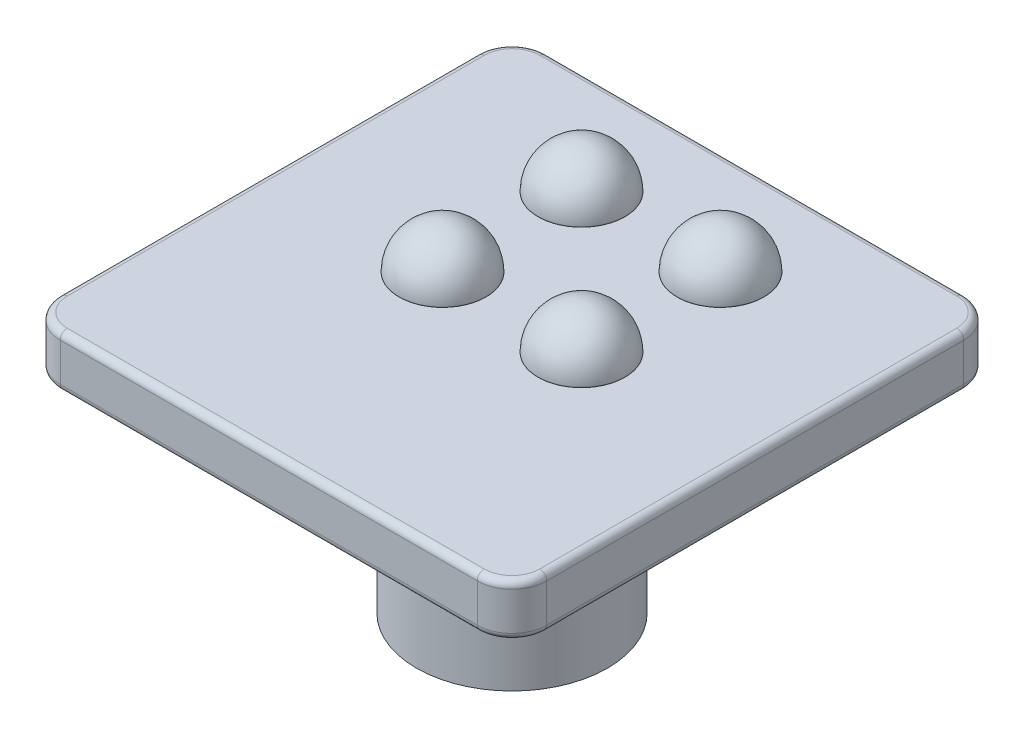
SolidWorks part; units mm, degrees
ref_plane "Front Plane" through (0, 0, 0) normal (0, 0, 1) x (1, 0, 0)
ref_plane "Top Plane" through (0, 0, 0) normal (0, 1, 0) x (1, 0, 0)
ref_plane "Right Plane" through (0, 0, 0) normal (1, 0, 0) x (0, 0, -1)
sketch "Sketch1" plane through (0, 0, 0) normal (0, 1, 0) x (1, 0, 0)
  line L1 (-7.3247, 4.3967) -> (4.6753, 4.3967)
  line L2 (-8.3247, 3.3967) -> (-8.3247, -8.6033)
  line L3 (-7.3247, -9.6033) -> (4.6753, -9.6033)
  line L4 (5.6753, 3.3967) -> (5.6753, -8.6033)
  arc A0 (-8.3247, -8.6033) -> (-7.3247, -9.6033) centre (-7.3247, -8.6033) ccw
  arc A1 (4.6753, -9.6033) -> (5.6753, -8.6033) centre (4.6753, -8.6033) ccw
  arc A2 (4.6753, 4.3967) -> (5.6753, 3.3967) centre (4.6753, 3.3967) cw
  arc A3 (-7.3247, 4.3967) -> (-8.3247, 3.3967) centre (-7.3247, 3.3967) ccw
  point P8 (5.6753, -9.6033)
  point P11 (5.6753, 4.3967)
  point P14 (-8.3247, 4.3967)
  dimension "D3" = 1
  dimension "D1" = 14
  dimension "D2" = 14
extrude "Boss-Extrude1" add sketch "Sketch1" along normal blind 1.5
sketch "Sketch2" plane through (0, 0, 0) normal (0, -1, 0) x (1, 0, 0)
  line L0 (-7.3247, 9.6033) -> (4.6753, 9.6033) construction
  line L1 (5.6753, 8.6033) -> (5.6753, -3.3967) construction
  line L2 (-1.3247, -4.3967) -> (-1.3247, 9.6033) construction
  line L3 (-8.3247, 2.6033) -> (5.6753, 2.6033) construction
  line L4 (-8.3247, -3.3967) -> (-8.3247, 8.6033) construction
  circle A0 centre (-1.3247, 2.6033) radius 2.75
  dimension "D1" = 7
  dimension "D2" = 7
extrude "Boss-Extrude2" add sketch "Sketch2" along normal blind 6
sketch "Sketch3" plane through (0, -6, 0) normal (0, -1, 0) x (1, 0, 0)
  line L0 (-1.3247, 5.3533) -> (-1.3247, -0.1467) construction
  line L1 (-3.3247, 3.1533) -> (0.6753, 3.1533)
  line L2 (-3.3247, 3.1533) -> (-3.3247, 2.0533)
  line L3 (-3.3247, 2.0533) -> (0.6753, 2.0533)
  line L4 (0.6753, 3.1533) -> (0.6753, 2.0533)
  line L5 (-1.8747, 4.6033) -> (-0.7747, 4.6033)
  line L6 (-1.8747, 4.6033) -> (-1.8747, 0.6033)
  line L7 (-1.8747, 0.6033) -> (-0.7747, 0.6033)
  line L8 (-0.7747, 4.6033) -> (-0.7747, 0.6033)
  line L9 (-4.0747, 2.6033) -> (1.4253, 2.6033) construction
  circle A3 centre (-1.3247, 2.6033) radius 2.75 construction
  circle A4 centre (-1.3247, 2.6033) radius 2.75 construction
  dimension "D7" = 0.55
  dimension "D1" = 4
  dimension "D2" = 1.1
  dimension "D3" = 1.1
  dimension "D4" = 4
  dimension "D5" = 2
  dimension "D6" = 2
  dimension "D8" = 0.55
extrude "Cut-Extrude1" cut sketch "Sketch3" against normal blind 6 contours L8 L5 L6 L1 | L1 L8 L3 L4 | L8 L1 L6 L3 | L6 L1 L2 L3 | L8 L3 L6 L7 region at (-2.5997, -6, 2.6033) region at (-1.3247, -6, 3.8783) region at (-1.3247, -6, 2.6033) region at (-0.0497, -6, 2.6033) region at (-1.3247, -6, 1.3283)
chamfer "Chamfer1" distance 0.3 angle 45 12 edges at (-1.3247, -6, 0.6033) (-1.8747, -6, 1.3283) (-2.5997, -6, 2.0533) (-3.3247, -6, 2.6033) (-2.5997, -6, 3.1533) (-0.7747, -6, 1.3283) (-0.0497, -6, 2.0533) (0.6753, -6, 2.6033) (-0.0497, -6, 3.1533) (-0.7747, -6, 3.8783) (-1.3247, -6, 4.6033) (-1.8747, -6, 3.8783)
fillet "Fillet1" radius 1 1 edges at (-1.3247, 0, -0.1467)
sketch "Sketch4" plane through (0, 1.5, 0) normal (0, 1, 0) x (1, 0, 0)
  line L0 (-1.3247, 4.3967) -> (-1.3247, -9.6033) construction
  line L1 (4.6753, 4.3967) -> (-7.3247, 4.3967) construction
  line L2 (-7.3247, -9.6033) -> (4.6753, -9.6033) construction
  line L3 (5.6753, -2.6033) -> (-8.3247, -2.6033) construction
  line L4 (-8.3247, 3.3967) -> (-8.3247, -8.6033) construction
  line L5 (5.6753, -8.6033) -> (5.6753, 3.3967) construction
  line L6 (-3.3247, 4.3967) -> (-3.3247, -9.6033) construction
  line L7 (0.6753, 4.3967) -> (0.6753, -9.6033) construction
  line L8 (-8.3247, 1.3967) -> (5.6753, 1.3967) construction
  line L9 (5.6753, -6.6033) -> (-8.3247, -6.6033) construction
  circle A0 centre (-3.3247, 1.3967) radius 1.25
  circle A1 centre (0.6753, -2.6033) radius 1.25
  circle A2 centre (-3.3247, -2.6033) radius 1.25
  circle A5 centre (0.6753, 1.3967) radius 1.25
  dimension "D1" = 4
  dimension "D2" = 4
  dimension "D3" = 2
  dimension "D4" = 2
extrude "Boss-Extrude3" add sketch "Sketch4" along normal blind 0.01
dome "Dome1" faces to dome 1 distance 1.25 reverse direction no elliptical dome no face at (-3.3247, 1.51, -0.1467) parameters "D1"=1.25
dome "Dome2" faces to dome 1 distance 1.25 reverse direction no elliptical dome no face at (0.6753, 1.51, -0.1467) parameters "D1"=1.25
dome "Dome3" faces to dome 1 distance 1.25 reverse direction no elliptical dome no face at (-3.3247, 1.51, 3.8533) parameters "D1"=1.25
dome "Dome4" faces to dome 1 distance 1.25 reverse direction no elliptical dome no face at (0.6753, 1.51, 3.8533) parameters "D1"=1.25
fillet "Fillet3" radius 0.2 16 edges at (5.3824, 1.5, -4.1038) (5.6753, 1.5, 2.6033) (5.3824, 1.5, 9.3104) (-1.3247, 1.5, 9.6033) (-8.0318, 1.5, 9.3104) (-8.0318, 1.5, -4.1038) (-8.3247, 1.5, 2.6033) (-1.3247, 1.5, -4.3967) (5.3824, 0, 9.3104) (5.6753, 0, 2.6033) (5.3824, 0, -4.1038) (-1.3247, 0, -4.3967) (-8.0318, 0, -4.1038) (-8.3247, 0, 2.6033) (-8.0318, 0, 9.3104) (-1.3247, 0, 9.6033)
